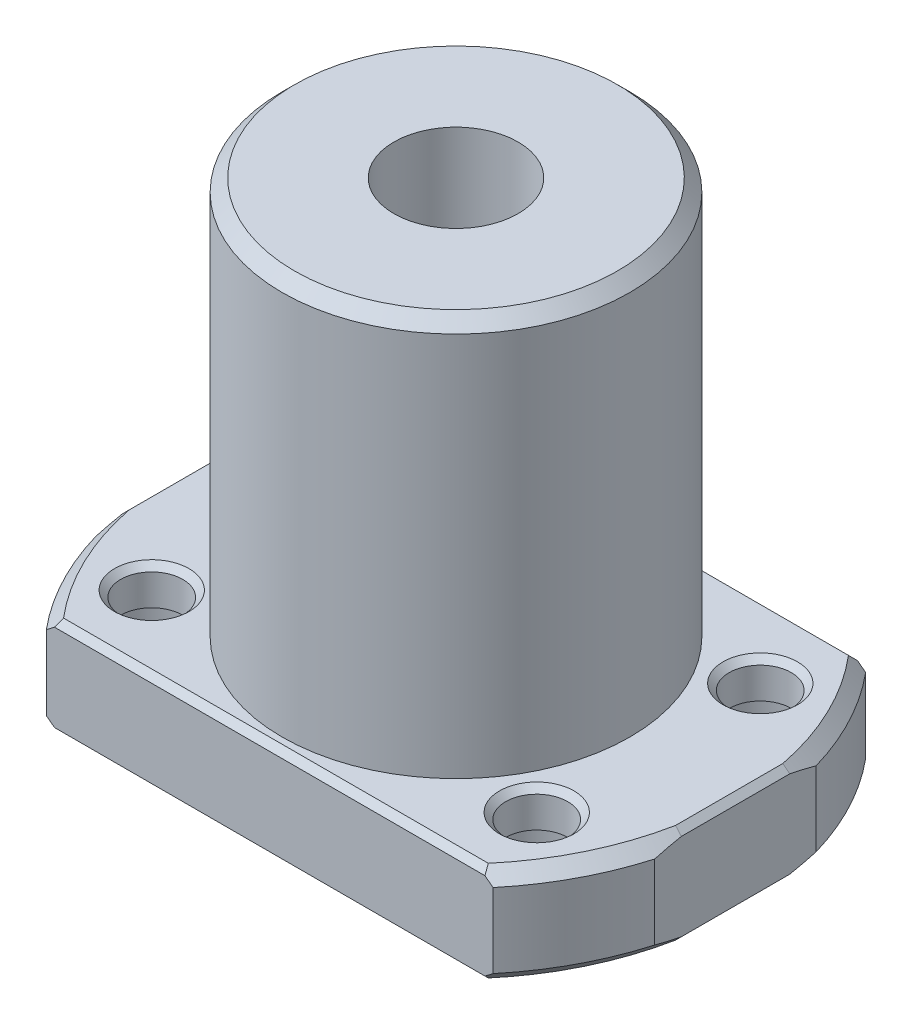
SolidWorks part; units mm, degrees
ref_plane "Front Plane" through (0, 0, 0) normal (0, 0, 1) x (1, 0, 0)
ref_plane "Top Plane" through (0, 0, 0) normal (0, 1, 0) x (1, 0, 0)
ref_plane "Right Plane" through (0, 0, 0) normal (1, 0, 0) x (0, 0, -1)
sketch "Sketch1" plane through (0, 0, 0) normal (0, 1, 0) x (1, 0, 0)
  circle A0 centre (0, 0) radius 14
  circle A1 centre (0, 0) radius 5
  dimension "D1" = 28
  dimension "D2" = 10
extrude "Boss-Extrude1" add sketch "Sketch1" along normal blind 32
sketch "Sketch2" plane through (0, 0, 0) normal (0, -1, 0) x (1, 0, 0)
  line L1 (-22.5, -15) -> (22.5, -15)
  line L2 (-22.5, -15) -> (-22.5, 15)
  line L3 (-22.5, 15) -> (22.5, 15)
  line L4 (22.5, -15) -> (22.5, 15)
  line L5 (-22.5, -15) -> (22.5, 15) construction
  line L6 (-22.5, 15) -> (22.5, -15) construction
  line L7 (-15.5, -9) -> (15.5, -9) construction
  line L8 (-15.5, -9) -> (-15.5, 9) construction
  line L9 (-15.5, 9) -> (15.5, 9) construction
  line L10 (15.5, -9) -> (15.5, 9) construction
  line L11 (-15.5, -9) -> (15.5, 9) construction
  line L12 (-15.5, 9) -> (15.5, -9) construction
  circle A0 centre (0, 0) radius 5
  circle A1 centre (-15.5, 9) radius 2.5
  circle A2 centre (15.5, 9) radius 2.5
  circle A3 centre (15.5, -9) radius 2.5
  circle A4 centre (-15.5, -9) radius 2.5
  circle A5 centre (0, 0) radius 23.4201
  point P0 (0, 0)
  point P17 (22.5, 6.5)
  point P18 (22.5, -6.5)
  circle M9 centre (0, 0) radius 14
  circle M10 centre (0, 0) radius 5
  dimension "D5" = 5
  dimension "D1" = 30
  dimension "D2" = 45
  dimension "D3" = 31
  dimension "D4" = 18
  dimension "D6" = 13
extrude "Boss-Extrude3" add sketch "Sketch2" along normal blind 8 contours M9 M10 | L1 A5 L4 L3 L2 A4 A3 A2 A1 M9 region at (-20.2067, 0, -10.7307) region at (-13.604, 0, 0)
sketch "Sketch3" plane through (0, -8, 0) normal (0, -1, 0) x (1, 0, 0)
  circle A0 centre (-15.5, 9) radius 4
  circle A1 centre (-15.5, -9) radius 4
  circle A2 centre (15.5, -9) radius 4
  circle A3 centre (15.5, 9) radius 4
  dimension "D1" = 8
extrude "Cut-Extrude1" cut sketch "Sketch3" against normal blind 5
chamfer "Chamfer2" distance 0.5 angle 45 12 edges at (22.5, -8, 0) (-22.5, -8, 0) (0, -8, -15) (0, -8, 15) (0, 0, -15) (-22.5, 0, 0) (22.5, 0, 0) (0, 0, 15) (15.5, 0, -11.5) (15.5, 0, 6.5) (-15.5, 0, -11.5) (-15.5, 0, 6.5)
chamfer "Chamfer3" distance 1 angle 45 9 edges at (20.4531, -8, -11.4092) (-20.4531, -8, -11.4092) (-20.4531, -8, 11.4092) (20.4531, -8, 11.4092) (20.4531, 0, -11.4092) (20.4531, 0, 11.4092) (-20.4531, 0, 11.4092) (-20.4531, 0, -11.4092) (0, 32, 14)
chamfer "Chamfer4" distance 0.5 angle 45 4 edges at (-15.5, -8, 5) (-15.5, -8, -13) (15.5, -8, 5) (15.5, -8, -13)
